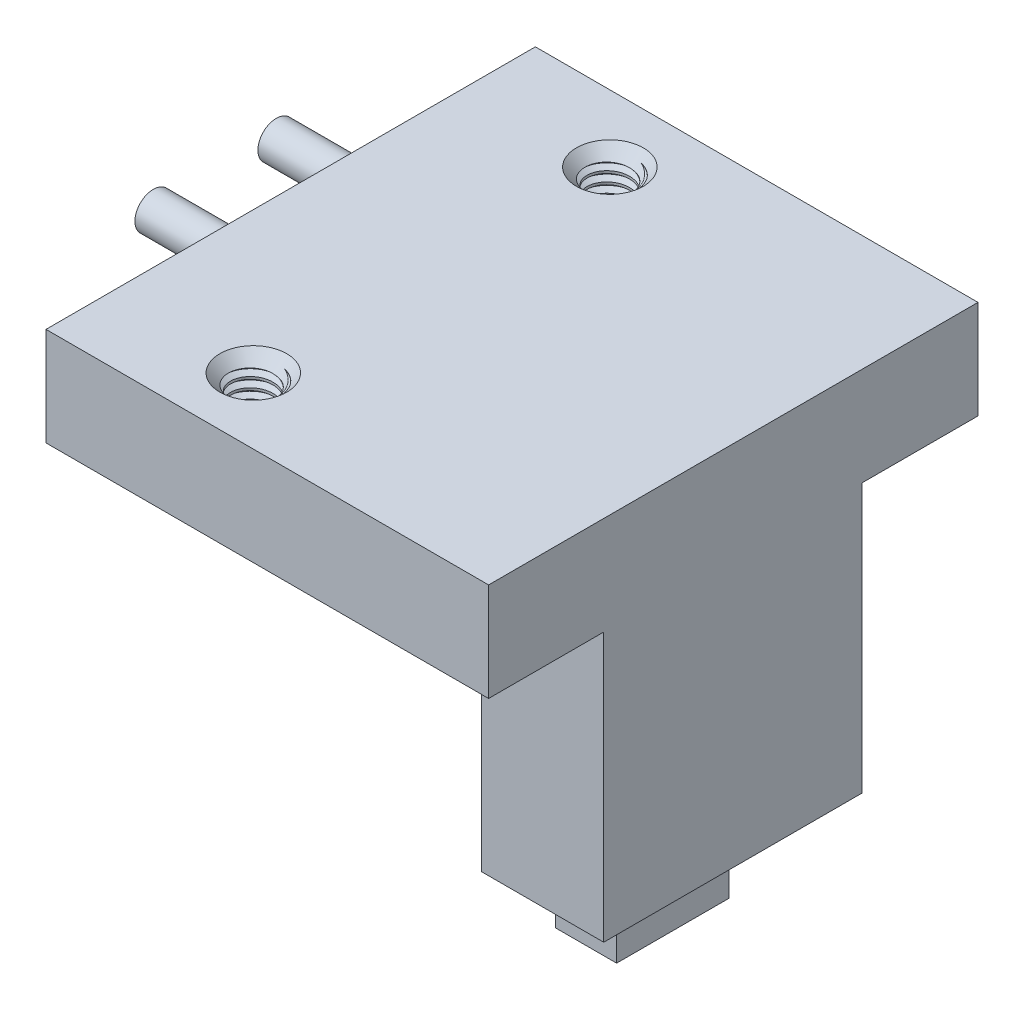
SolidWorks part; units mm, degrees
ref_plane "Front Plane" through (0, 0, 0) normal (0, 0, 1) x (1, 0, 0)
ref_plane "Top Plane" through (0, 0, 0) normal (0, 1, 0) x (1, 0, 0)
ref_plane "Right Plane" through (0, 0, 0) normal (1, 0, 0) x (0, 0, -1)
sketch "Sketch1" plane through (0, 0, 0) normal (0, 1, 0) x (1, 0, 0)
  line L1 (-13.9179, 31.2256) -> (22.0821, 31.2256)
  line L2 (-13.9179, 31.2256) -> (-13.9179, -5.7744)
  line L3 (-13.9179, -5.7744) -> (22.0821, -5.7744)
  line L4 (22.0821, 31.2256) -> (22.0821, -5.7744)
  dimension "D1" = 37
  dimension "D2" = 36
extrude "Boss-Extrude1" add sketch "Sketch1" along normal blind 5
sketch "Sketch2" plane through (0, 0, 0) normal (0, -1, 0) x (1, 0, 0)
  line L5 (-13.9179, -31.2256) -> (22.0821, -31.2256)
  line L6 (-13.9179, -31.2256) -> (-13.9179, -23.2256)
  line L7 (-13.9179, -23.2256) -> (22.0821, -23.2256)
  line L8 (22.0821, 5.7744) -> (22.0821, -31.2256) construction
  line L9 (-13.9179, 5.7744) -> (22.0821, 5.7744)
  line L10 (-13.9179, 5.7744) -> (-13.9179, -2.2256)
  line L11 (-13.9179, -2.2256) -> (22.0821, -2.2256)
  line L12 (22.0821, 5.7744) -> (22.0821, -2.2256)
  line L13 (22.0821, -31.2256) -> (22.0821, -23.2256)
  dimension "D1" = 8
  dimension "D2" = 8
extrude "Boss-Extrude2" add sketch "Sketch2" along normal blind 3
sketch "Sketch3" plane through (-13.9179, 0, 0) normal (-1, 0, 0) x (0, 0, 1)
  line L0 (-17.5956, 3) -> (-7.5956, 3) construction
  line L2 (5.7744, -3) -> (-2.2256, -3) construction
  line L5 (-2.2256, -3) -> (-2.2256, 0) construction
  circle A0 centre (-17.5956, 3) radius 1.5
  circle A1 centre (-7.5956, 3) radius 1.5
  dimension "D4" = 3
  dimension "D5" = 3
  dimension "D1" = 6
  dimension "D2" = 10
  dimension "D3" = 5.37
  dimension "D6" = 6
extrude "Boss-Extrude3" add sketch "Sketch3" along normal blind 6
sketch "Sketch5" [suppressed] plane through (0, -3, 0) normal (0, -1, 0) x (1, 0, 0)
  line L0 (22.0821, -16.1556) -> (22.0821, -9.2956) construction
  line L1 (-13.9179, -16.1556) -> (22.0821, -16.1556)
  line L2 (-13.9179, -16.1556) -> (-13.9179, -1.6556)
  line L3 (-13.9179, -1.6556) -> (22.0821, -1.6556)
  line L4 (22.0821, -16.1556) -> (22.0821, -1.6556)
  line L6 (22.0821, -23.7956) -> (-13.9179, -23.7956)
  line L7 (22.0821, -23.7956) -> (22.0821, -9.2956)
  line L8 (22.0821, -9.2956) -> (-13.9179, -9.2956)
  line L9 (-13.9179, -23.7956) -> (-13.9179, -9.2956)
  dimension "D1" = 14.5
  dimension "D2" = 14.5
sketch "Sketch18" plane through (0, 0, 0) normal (0, -1, 0) x (1, 0, 0)
  line L0 (-13.9179, -2.2256) -> (22.0821, -2.2256) construction
  line L1 (22.0821, -23.2256) -> (12.128, -23.2256)
  line L2 (22.0821, -23.2256) -> (22.0821, -2.2256)
  line L3 (22.0821, -2.2256) -> (12.128, -2.2256)
  line L4 (12.128, -23.2256) -> (12.128, -2.2256)
extrude "Boss-Extrude8" add sketch "Sketch18" along normal blind 24.85
sketch "Sketch19" plane through (0, -24.85, 0) normal (0, -1, 0) x (1, 0, 0)
  line L1 (17.0821, -8.2756) -> (12.128, -8.2756)
  line L2 (17.0821, -8.2756) -> (17.0821, -17.4256)
  line L3 (17.0821, -17.4256) -> (12.128, -17.4256)
  line L4 (12.128, -8.2756) -> (12.128, -17.4256)
  line L6 (22.0821, -2.2256) -> (12.128, -2.2256) construction
  line L7 (7.0821, -23.4756) -> (22.0821, -23.4756) construction
  dimension "D1" = 6.05
  dimension "D2" = 6.05
extrude "Boss-Extrude9" add sketch "Sketch19" along normal blind 7
extrude "Boss-Extrude4" [suppressed] add sketch "Sketch5" along normal blind 9.85
sketch "Sketch6" [suppressed] plane through (0, -3, 0) normal (0, -1, 0) x (1, 0, 0)
  line L1 (12.1663, -2.4117) -> (22.1663, -2.4117)
  line L2 (12.1663, -2.4117) -> (12.1663, -24.2717)
  line L3 (12.1663, -24.2717) -> (22.1663, -24.2717)
  line L4 (22.1663, -2.4117) -> (22.1663, -24.2717)
  dimension "D1" = 10
extrude "Boss-Extrude5" [suppressed] add sketch "Sketch6" along normal blind 9.85
sketch "Sketch7" [suppressed] plane through (0, -12.85, 0) normal (0, -1, 0) x (1, 0, 0)
  line L1 (17.6799, -8.9298) -> (11.9799, -8.9298)
  line L2 (17.6799, -8.9298) -> (17.6799, -17.7798)
  line L3 (17.6799, -17.7798) -> (11.9799, -17.7798)
  line L4 (11.9799, -8.9298) -> (11.9799, -17.7798)
  dimension "D1" = 8.85
  dimension "D2" = 5.7
extrude "Boss-Extrude6" [suppressed] add sketch "Sketch7" along normal blind 12
sketch "Sketch8" plane through (0, 5, 0) normal (0, 1, 0) x (1, 0, 0)
  line L0 (-13.9179, 31.2256) -> (-2.4179, 31.2256) construction
  line L1 (22.0821, 31.2256) -> (-13.9179, 31.2256) construction
  line L2 (-2.4179, 31.2256) -> (-2.4179, 27.2256) construction
  line L3 (-13.9179, -5.7744) -> (-2.4179, -5.7744) construction
  line L4 (-13.9179, -5.7744) -> (22.0821, -5.7744) construction
  line L5 (-2.4179, -5.7744) -> (-2.4179, -1.7744) construction
  circle A0 centre (-2.4179, 27.2256) radius 2
  circle A1 centre (-2.4179, -1.7744) radius 2
  dimension "D3" = 4
  dimension "D1" = 11.5
  dimension "D2" = 4
sketch "Sketch17" [suppressed] plane through (0, 0, 0) normal (0, -1, 0) x (1, 0, 0)
  line L1 (-13.8337, 27.1583) -> (22.1663, 27.1583)
  line L2 (-13.8337, 27.1583) -> (-13.8337, 12.0883)
  line L3 (-13.8337, 12.0883) -> (22.1663, 12.0883)
  line L4 (22.1663, 27.1583) -> (22.1663, 12.0883)
  line L5 (-13.8337, -38.7717) -> (22.1663, -38.7717)
  line L6 (-13.8337, -38.7717) -> (-13.8337, -53.8417)
  line L7 (-13.8337, -53.8417) -> (22.1663, -53.8417)
  line L8 (22.1663, -38.7717) -> (22.1663, -53.8417)
extrude "Boss-Extrude7" [suppressed] add sketch "Sketch17" along normal blind 2.05
hole_wizard "#8-32 Tapped Hole2" positions "Sketch16" profile "Sketch15" tap size "#8-32" standard "ANSI Inch"
sketch "Sketch16" plane through (0, 5, 0) normal (0, 1, 0) x (1, 0, 0)
  point P0 (-2.4179, 27.2256)
  point P3 (-2.4179, -1.7744)
sketch "Sketch15" plane through (-2.4179, 5, -27.2256) normal (1, 0, 0) x (0, 0, 1)
  line L0 (0, 0) -> (0, 12)
  line L1 (0, 12) -> (1.7272, 10.9622)
  line L2 (1.7272, 10.9622) -> (1.7272, 0.9906)
  line L3 (1.7272, 0.9906) -> (2.7178, 0)
  line L5 (2.7178, 0) -> (0, 0)
  line L6 (-1.7272, 0.9906) -> (-2.7178, 0) construction
  line L10 (0, 12) -> (-1.7272, 10.9622) construction
  line L11 (0, -6.35) -> (0, 107.95) construction
  dimension "Tap Drill Dia." = 3.4544
  dimension "Tap Drill Depth" = 12
  dimension "Near C'Sink Dia." = 5.4356
  dimension "Near C'Sink Angle" = 90
  dimension "Drill Angle" = 118
cosmetic thread "Hole Thread1" parameters "D1"=8.33, "D2"=4.1656
cosmetic thread "Hole Thread2" parameters "D1"=8.33, "D2"=4.1656
thread "Thread4" pitch 0.7937 method cut profile "Thread Profile10" start angle 0, offset 1, length 10, pitch 0.7937, diameter 3.4544
ref_plane "Plane10" through (-4.1451, 5.0094, -27.2256) normal (0, 0, 1) x (-1, 0, 0)
sketch "Thread Profile10" plane through (-4.1451, 5.0094, -27.2256) normal (0, 0, 1) x (-1, 0, 0)
  line L0 (0, 0) -> (0, 0.7937) construction
  line L1 (0, 0) -> (0.4296, 0.248)
  line L2 (0.4296, 0.248) -> (0.4296, 0.3473)
  line L3 (0.4296, 0.3473) -> (0, 0.5953)
  line L4 (0.4296, 0.2977) -> (0, 0.2977) construction
  line L11 (0, 0) -> (0, 0.5953)
  point P2 (0, 0)
  dimension "Pitch" = 0.7937
  dimension "Profile_Angle" = 60
  dimension "Profile_Land" = 0.0992
  dimension "Profile_Height" = 0.4296
thread "Thread5" pitch 0.7937 method cut profile "Thread Profile11" start angle 0, offset 1, length 10, pitch 0.7937, diameter 3.4544
ref_plane "Plane11" through (-4.1451, 5.0094, 1.7744) normal (0, 0, 1) x (-1, 0, 0)
sketch "Thread Profile11" plane through (-4.1451, 5.0094, 1.7744) normal (0, 0, 1) x (-1, 0, 0)
  line L0 (0, 0) -> (0, 0.7937) construction
  line L1 (0, 0) -> (0.4296, 0.248)
  line L2 (0.4296, 0.248) -> (0.4296, 0.3473)
  line L3 (0.4296, 0.3473) -> (0, 0.5953)
  line L4 (0.4296, 0.2977) -> (0, 0.2977) construction
  line L11 (0, 0) -> (0, 0.5953)
  point P2 (0, 0)
  dimension "Pitch" = 0.7937
  dimension "Profile_Angle" = 60
  dimension "Profile_Land" = 0.0992
  dimension "Profile_Height" = 0.4296
sketch "Sketch20" plane through (0, 5, 0) normal (0, 1, 0) x (1, 0, 0)
  line L0 (-13.9179, 31.2256) -> (22.0821, 31.2256)
  line L1 (-13.9179, 31.2256) -> (-13.9179, 32.6679)
  line L2 (22.0821, 31.2256) -> (22.0821, 32.6679)
  line L3 (-13.9179, 32.6679) -> (22.0821, 32.6679)
  line L4 (-13.9179, -5.7744) -> (22.0821, -5.7744)
  line L5 (-13.9179, -5.7744) -> (-13.9179, -7.1354)
  line L6 (22.0821, -5.7744) -> (22.0821, -7.1354)
  line L7 (-13.9179, -7.1354) -> (22.0821, -7.1354)
extrude "Boss-Extrude10" add sketch "Sketch20" against normal blind 8
